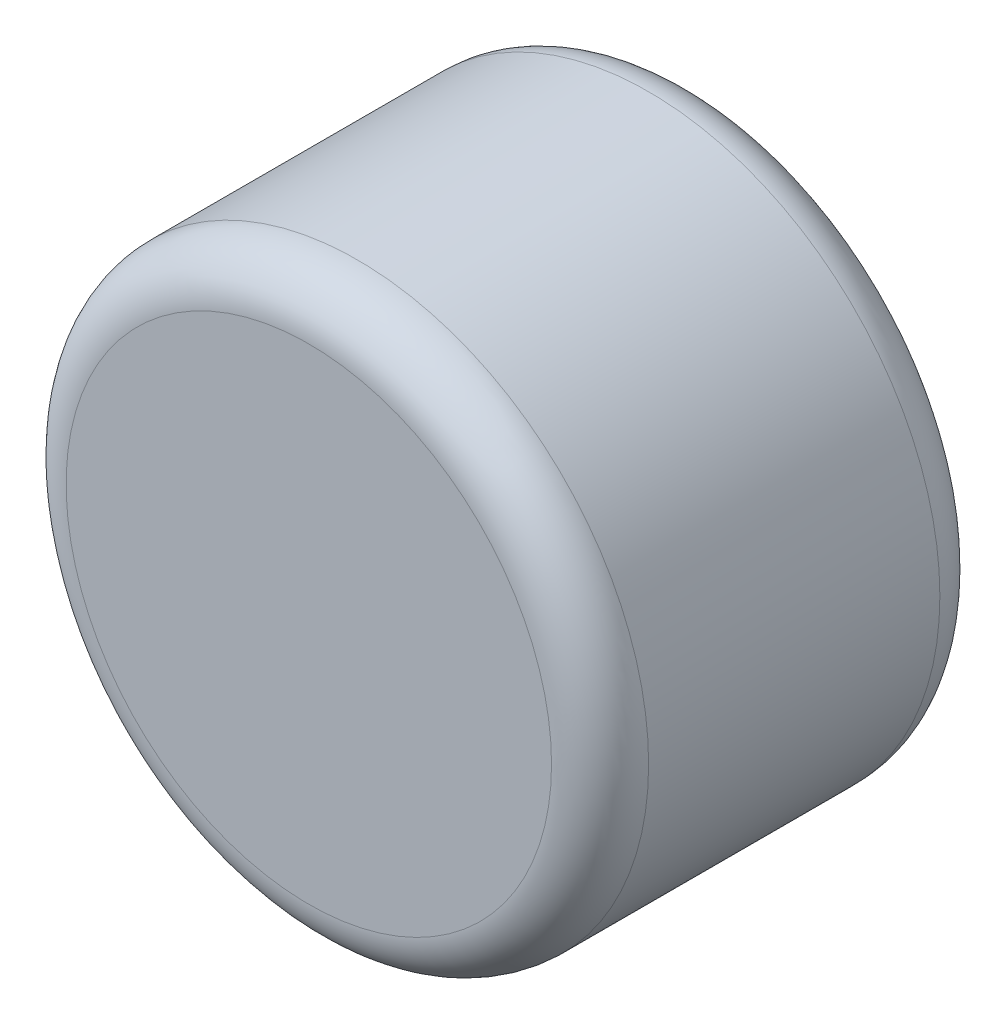
SolidWorks part; units mm, degrees
ref_plane "Piano frontale" through (0, 0, 0) normal (0, 0, 1) x (1, 0, 0)
ref_plane "Piano superiore" through (0, 0, 0) normal (0, 1, 0) x (1, 0, 0)
ref_plane "Piano destro" through (0, 0, 0) normal (1, 0, 0) x (0, 0, -1)
sketch "Schizzo1" plane through (0, 0, 0) normal (0, 0, 1) x (1, 0, 0)
  circle A0 centre (0, 0) radius 3
  dimension "D1" = 6
extrude "Estrusione-Estrusione1" add sketch "Schizzo1" along normal blind 4
fillet "Raccordo1" radius 0.5 2 edges at (3, 0, 0) (3, 0, 4)
